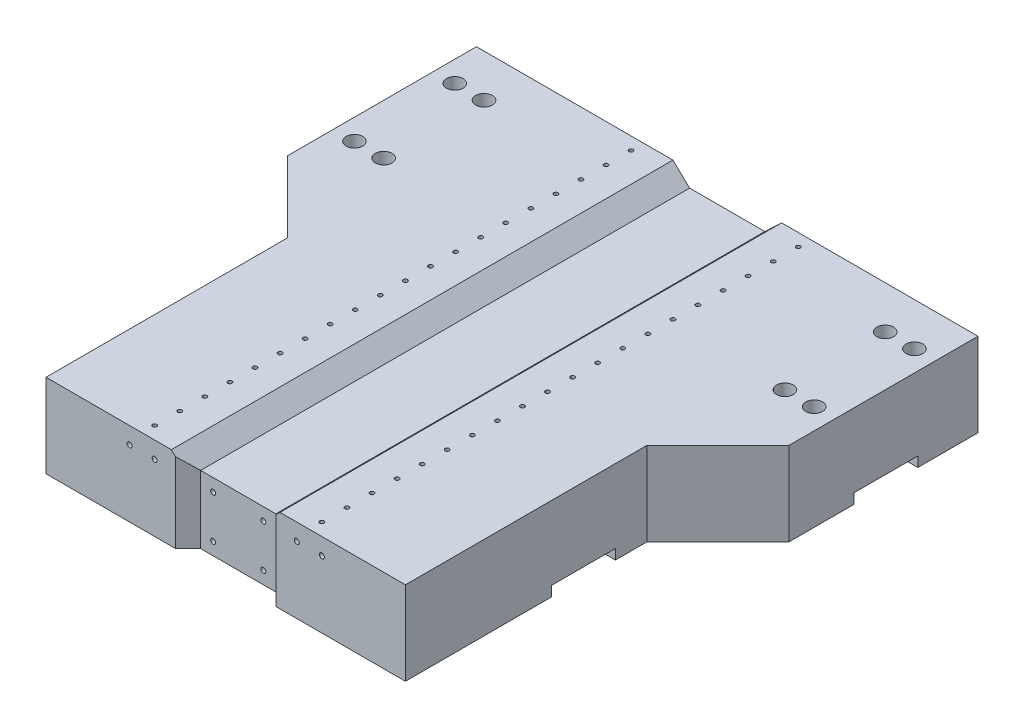
SolidWorks part; units mm, degrees
ref_plane "Front Plane" through (0, 0, 0) normal (0, 0, 1) x (1, 0, 0)
ref_plane "Top Plane" through (0, 0, 0) normal (0, 1, 0) x (1, 0, 0)
ref_plane "Right Plane" through (0, 0, 0) normal (1, 0, 0) x (0, 0, -1)
sketch "Sketch1" plane through (0, 0, 0) normal (0, 1, 0) x (1, 0, 0)
  line L1 (-300, 300) -> (300, 300)
  line L2 (-300, 300) -> (-300, -300)
  line L3 (-300, -300) -> (300, -300)
  line L4 (300, 300) -> (300, -300)
  line L5 (0, -300) -> (0, 300) construction
  line L6 (-300, 0) -> (300, 0) construction
  point P0 (0, 0)
  dimension "D1" = 600
extrude "Boss-Extrude1" add sketch "Sketch1" along normal blind 100
sketch "Sketch2" plane through (0, 100, 0) normal (0, 1, 0) x (1, 0, 0)
  line L0 (-300, -300) -> (-220, -300)
  line L9 (-300, -300) -> (300, -300) construction
  line L11 (300, -300) -> (220, -300)
  line L13 (-300, 300) -> (-300, -300) construction
  line L15 (-300, -300) -> (-300, 60)
  line L16 (300, -300) -> (300, 60)
  line L38 (-300, 60) -> (-300, 74)
  line L41 (300, 60) -> (300, 74)
  line L45 (-220, 74) -> (-300, 74)
  line L48 (220, 74) -> (300, 74)
  line L49 (-220, 74) -> (-215, 74)
  line L50 (-215, 74) -> (-215, -300)
  line L51 (-215, -300) -> (-220, -300)
  line L52 (220, 74) -> (215, 74)
  line L53 (215, 74) -> (215, -300)
  line L54 (215, -300) -> (220, -300)
extrude "Cut-Extrude1" cut sketch "Sketch2" against normal through all
chamfer "Chamfer5" distance 85 angle 45 2 edges at (-215, 50, -74) (215, 50, -74)
sketch "Sketch3" plane through (0, 0, 300) normal (0, 0, 1) x (1, 0, 0)
  line L0 (-35, 81) -> (-45, 81)
  line L2 (35, 81) -> (45, 81)
  line L4 (0, 81) -> (35, 81)
  line L8 (0, 81) -> (-35, 81)
  line L10 (-45, 100) -> (45, 100)
  line L13 (-215, 100) -> (215, 100) construction
  line L14 (-65, 100) -> (-45, 100)
  line L17 (45, 100) -> (65, 100)
  line L22 (-45, 81) -> (-65, 100)
  line L23 (45, 81) -> (65, 100)
extrude "Cut-Extrude2" cut sketch "Sketch3" against normal through all
sketch "Sketch9" plane through (0, 100, 0) normal (0, 1, 0) x (1, 0, 0)
  circle A0 centre (275, 129) radius 10
  circle A1 centre (240, 129) radius 10
  circle A3 centre (240, 249) radius 10
  circle A5 centre (275, 249) radius 10
  circle A6 centre (-275, 129) radius 10
  circle A7 centre (-240, 249) radius 10
  circle A8 centre (-275, 249) radius 10
  circle A11 centre (-240, 129) radius 10
  circle A12 centre (240, 189) radius 10 [skipped]
  circle A13 centre (275, 189) radius 10 [skipped]
  dimension "D1" = 2
  dimension "D2" = 3
extrude "Cut-Extrude5" cut sketch "Sketch9" against normal through all
sketch "Sketch12" plane through (0, 100, 0) normal (0, 1, 0) x (1, 0, 0)
  circle A40 centre (-100, -285) radius 2.5
  circle A41 centre (100, -285) radius 2.5
  circle A42 centre (100, -255) radius 2.5
  circle A43 centre (100, -225) radius 2.5
  circle A44 centre (100, -195) radius 2.5
  circle A45 centre (100, -165) radius 2.5
  circle A46 centre (100, -135) radius 2.5
  circle A47 centre (100, -105) radius 2.5
  circle A48 centre (100, -75) radius 2.5
  circle A49 centre (100, -45) radius 2.5
  circle A50 centre (100, -15) radius 2.5
  circle A51 centre (100, 15) radius 2.5
  circle A52 centre (100, 45) radius 2.5
  circle A53 centre (100, 75) radius 2.5
  circle A54 centre (100, 105) radius 2.5
  circle A55 centre (100, 135) radius 2.5
  circle A56 centre (100, 165) radius 2.5
  circle A57 centre (100, 195) radius 2.5
  circle A58 centre (100, 225) radius 2.5
  circle A59 centre (100, 255) radius 2.5
  circle A60 centre (100, 285) radius 2.5
  circle A61 centre (-100, -255) radius 2.5
  circle A62 centre (-100, -225) radius 2.5
  circle A63 centre (-100, -195) radius 2.5
  circle A64 centre (-100, -165) radius 2.5
  circle A65 centre (-100, -135) radius 2.5
  circle A66 centre (-100, -105) radius 2.5
  circle A67 centre (-100, -75) radius 2.5
  circle A68 centre (-100, -45) radius 2.5
  circle A69 centre (-100, -15) radius 2.5
  circle A70 centre (-100, 15) radius 2.5
  circle A71 centre (-100, 45) radius 2.5
  circle A72 centre (-100, 75) radius 2.5
  circle A73 centre (-100, 105) radius 2.5
  circle A74 centre (-100, 135) radius 2.5
  circle A75 centre (-100, 165) radius 2.5
  circle A76 centre (-100, 195) radius 2.5
  circle A77 centre (-100, 225) radius 2.5
  circle A78 centre (-100, 255) radius 2.5
  circle A79 centre (-100, 285) radius 2.5
  dimension "D1" = 2
  dimension "D2" = 20
extrude "Cut-Extrude7" cut sketch "Sketch12" against normal blind 30
sketch "Sketch14" plane through (0, 81, 0) normal (0, 1, 0) x (1, 0, 0)
  line L5 (-45, -300) -> (45, -300)
  line L6 (-45, -300) -> (-45, -285)
  line L11 (45, -285) -> (45, -300)
  line L15 (-45, -285) -> (45, -285)
extrude "Cut-Extrude8" cut sketch "Sketch14" against normal through all
chamfer "Chamfer3" distance 15 angle 45 2 edges at (45, 40.5, 300) (-45, 40.5, 300)
sketch "Sketch15" plane through (-300, 0, 0) normal (-1, 0, 0) x (0, 0, 1)
  line L0 (125, -0.7) -> (125, 12) construction
  line L1 (125, 12) -> (48.8, 12) construction
  line L2 (48.8, 12) -> (48.8, -0.7) construction
  line L3 (48.8, -0.7) -> (125, -0.7) construction
  line L4 (-228, 12) -> (-228, -0.7) construction
  line L5 (-228, -0.7) -> (-151.8, -0.7) construction
  line L6 (-151.8, -0.7) -> (-151.8, 12) construction
  line L7 (-151.8, 12) -> (-228, 12) construction
  line L8 (125, -0.7) -> (125, 12)
  line L9 (125, 12) -> (48.8, 12)
  line L10 (48.8, 12) -> (48.8, -0.7)
  line L11 (48.8, -0.7) -> (125, -0.7)
  line L12 (-228, 12) -> (-228, -0.7)
  line L13 (-228, -0.7) -> (-151.8, -0.7)
  line L14 (-151.8, -0.7) -> (-151.8, 12)
  line L15 (-151.8, 12) -> (-228, 12)
extrude "Cut-Extrude9" cut sketch "Sketch15" against normal through all
sketch "Sketch22" plane through (0, 0, -300) normal (0, 0, -1) x (-1, 0, 0)
  line L0 (-45, 81) -> (-45, 0)
  line L1 (-300, 0) -> (300, 0) construction
  line L2 (-45, 0) -> (45, 0)
  line L3 (45, 0) -> (45, 81)
  line L4 (45, 81) -> (-45, 81)
sketch "Sketch17" plane through (0, 0, 285) normal (0, 0, 1) x (1, 0, 0)
  line L8 (30, 66) -> (-30, 66)
  line L9 (-30, 66) -> (-30, 15)
  line L10 (-30, 15) -> (30, 15)
  line L11 (30, 15) -> (30, 66)
  line L12 (30, 66) -> (-30, 66)
  line L13 (-30, 66) -> (-30, 15)
  line L14 (-30, 15) -> (30, 15)
  line L15 (30, 15) -> (30, 66)
  dimension "D1" = 15
sketch "Sketch19" plane through (0, 0, -300) normal (0, 0, -1) x (-1, 0, 0)
  line L0 (30, 66) -> (30, 15) construction
  line L1 (30, 15) -> (-30, 15) construction
  line L2 (-30, 15) -> (-30, 66) construction
  line L3 (-30, 66) -> (30, 66) construction
  line L4 (30, 66) -> (30, 15)
  line L5 (30, 15) -> (-30, 15)
  line L6 (-30, 15) -> (-30, 66)
  line L7 (-30, 66) -> (30, 66)
sketch "Sketch20" plane through (0, 0, 300) normal (0, 0, 1) x (1, 0, 0)
  line L2 (85, 100) -> (85, 80)
  line L4 (-215, 100) -> (-65, 100) construction
  line L5 (-85, 100) -> (-85, 80)
  line L6 (115, 100) -> (115, 80)
  line L7 (-115, 100) -> (-115, 80)
  line L8 (0, 34.1921) -> (0, 91.6213)
sketch "Sketch21" plane through (0, 0, -300) normal (0, 0, -1) x (-1, 0, 0)
  line L0 (-115, 100) -> (-115, 80) construction
  line L1 (-85, 100) -> (-85, 80) construction
  line L2 (85, 100) -> (85, 80) construction
  line L3 (115, 100) -> (115, 80) construction
  line L4 (-115, 100) -> (-115, 80)
  line L5 (-85, 100) -> (-85, 80)
  line L6 (85, 100) -> (85, 80)
  line L7 (115, 100) -> (115, 80)
hole_wizard "Ø6.0mm Dowel Hole1" positions "3DSketch2" profile "Sketch18" hole size "Ø6.0" standard "ANSI Metric"
sketch3d "3DSketch2"
  point P0 (-30, 66, 285)
  point P3 (30, 66, 285)
  point P6 (30, 15, 285)
  point P9 (-30, 15, 285)
  point P13 (30, 66, -300)
  point P16 (-30, 66, -300)
  point P19 (-30, 15, -300)
  point P22 (30, 15, -300)
  point P26 (-85, 80, 300)
  point P29 (-115, 80, 300)
  point P32 (85, 80, 300)
  point P35 (115, 80, 300)
  point P38 (-115, 80, -300)
  point P41 (-85, 80, -300)
  point P44 (85, 80, -300)
  point P47 (115, 80, -300)
sketch "Sketch18" plane through (-30, 66, 285) normal (1, 0, 0) x (0, -1, 0)
  line L0 (0, 0) -> (0, 31.8026)
  line L1 (0, 31.8026) -> (3, 30)
  line L2 (3, 30) -> (3, 0)
  line L5 (3, 0) -> (0, 0)
  line L10 (0, 31.8026) -> (-3, 30) construction
  line L11 (0, -6.35) -> (0, 107.95) construction
  dimension "Hole Dia." = 6
  dimension "Hole Depth" = 30
  dimension "Drill Angle" = 118
